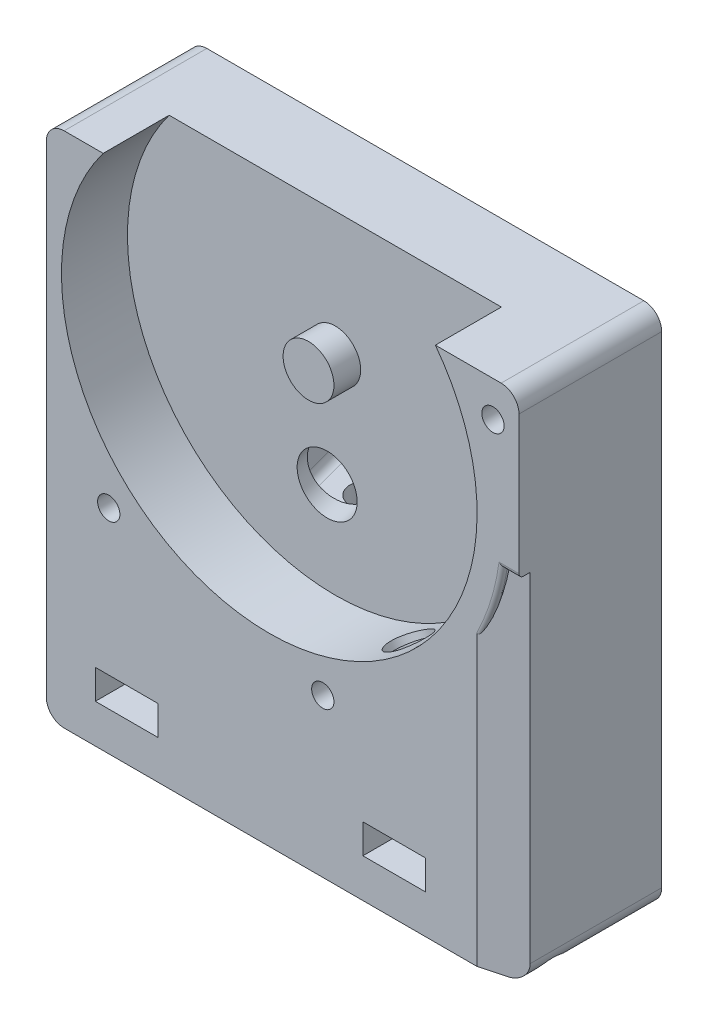
SolidWorks part; units mm, degrees
ref_plane "Front" through (0, 0, 0) normal (0, 0, 1) x (1, 0, 0)
ref_plane "Top" through (0, 0, 0) normal (0, 1, 0) x (1, 0, 0)
ref_plane "Right" through (0, 0, 0) normal (1, 0, 0) x (0, 0, -1)
sketch "Sketch1" plane through (0, 0, 0) normal (0, 0, 1) x (1, 0, 0)
  line L1 (-25, 27) -> (28, 27)
  line L2 (-25, 27) -> (-25, -31)
  line L3 (-25, -31) -> (28, -31)
  line L4 (28, 27) -> (28, -31)
  dimension "D1" = 58
  dimension "D2" = 53
  dimension "D3" = 31
  dimension "D4" = 25
extrude "Boss-Extrude1" add sketch "Sketch1" along normal blind 4 and the other way blind 12
sketch "Sketch2" plane through (0, 0, 0) normal (0, 0, 1) x (1, 0, 0)
  circle A1 centre (0, 13) radius 23.3
  dimension "D1" = 46.6
  dimension "D2" = 13
extrude "Cut-Extrude1" cut sketch "Sketch2" along normal blind 4 and the other way blind 3.4
sketch "Sketch3" plane through (0, 0, -3.4) normal (0, 0, 1) x (1, 0, 0)
  circle A0 centre (0, 13) radius 2.85
  arc A1 (-18.625, 27) -> (18.625, 27) centre (0, 13) ccw construction
  dimension "D1" = 5.7
extrude "Boss-Extrude2" add sketch "Sketch3" along normal blind 3
ref_plane "Plane1" through (0, 13, 0) normal (0, 1, 0) x (1, 0, 0)
ref_axis "Axis1" through (0, 13, -80.9) along (0, 0, 1)
ref_plane "Plane2" through (5.6292, 3.25, 0) normal (0.866, 0.5, 0) x (0, 0, 1)
ref_plane "Plane3" through (-5.6292, 9.75, 0) normal (-0.5, 0.866, 0) x (0, 0, 1)
ref_plane "Plane4" through (21.3708, -37.0154, 0) normal (-0.5, 0.866, 0) x (0, 0, 1)
sketch "Sketch4" plane through (21.3708, -37.0154, 0) normal (-0.5, 0.866, 0) x (0, 0, 1)
  line L0 (88.99, 6.5) -> (-88.99, 6.5) construction
  line L1 (4, 8.7487) -> (4, 37.7487) construction
  circle A0 centre (0, 6.5) radius 2.25
  dimension "D1" = 4.5
  dimension "D2" = 4
extrude "Cut-Extrude2" cut sketch "Sketch4" along normal blind 32
sketch "Sketch5" plane through (21.3708, -37.0154, 0) normal (-0.5, 0.866, 0) x (0, 0, 1)
  circle A0 centre (0, 6.5) radius 2.6
  arc A1 (-0.0761, 8.7487) -> (0.0761, 8.7487) centre (0, 6.5) ccw construction
  dimension "D1" = 5.2
extrude "Cut-Extrude3" cut sketch "Sketch5" along normal blind 30
ref_axis "Axis2" through (0, 50, 0) along (0, -1, 0)
ref_plane "Plane5" through (0, 0, 0) normal (0.2588, 0, 0.9659) x (0, -1, 0)
sketch "Sketch6" plane through (0, 0, 0) normal (0.2588, 0, 0.9659) x (0, -1, 0)
  circle A0 centre (0, 0) radius 3.25
  dimension "D1" = 6.5
extrude "Cut-Extrude4" cut sketch "Sketch6" against normal through all
ref_axis "Axis3" through (-3.3331, 0, -12.4392) along (0.2588, 0, 0.9659)
ref_plane "Plane6" through (-3.6235, 0, -13.523) normal (0.2588, 0, 0.9659) x (0, -1, 0)
sketch "Sketch10" plane through (-3.6235, 0, -13.523) normal (0.2588, 0, 0.9659) x (0, -1, 0)
  line L1 (4, 5) -> (-4, 5)
  line L2 (5, 4) -> (5, -4)
  line L3 (4, -5) -> (-4, -5)
  line L4 (-5, 4) -> (-5, -4)
  line L5 (5, 5) -> (-5, -5) construction
  line L6 (5, -5) -> (-5, 5) construction
  arc A0 (-4, 5) -> (-5, 4) centre (-4, 4) ccw
  arc A1 (-5, -4) -> (-4, -5) centre (-4, -4) ccw
  arc A2 (4, -5) -> (5, -4) centre (4, -4) ccw
  arc A3 (5, 4) -> (4, 5) centre (4, 4) ccw
  point P0 (0, 0)
  dimension "D3" = 1
  dimension "D1" = 10
  dimension "D2" = 10
extrude "Cut-Extrude5" cut sketch "Sketch10" along normal blind 8
sketch "Sketch11" plane through (0, -31, 0) normal (0, -1, 0) x (1, 0, 0)
  line L0 (-3.3331, -12.4392) -> (-0.1584, -0.591) construction
  line L1 (-5.4166, -4.7603) -> (2.3108, -6.8308) construction
  circle A0 centre (-2.5882, -9.6593) radius 1.5
  dimension "D1" = 3
  dimension "D2" = 4
extrude "Cut-Extrude6" cut sketch "Sketch11" against normal blind 27
sketch "Sketch12" plane through (0, -31, 0) normal (0, -1, 0) x (1, 0, 0)
  circle A0 centre (-2.5882, -9.6593) radius 2
  dimension "D1" = 4
extrude "Cut-Extrude7" cut sketch "Sketch12" against normal blind 27
sketch "Sketch13" plane through (0, 0, 4) normal (0, 0, 1) x (1, 0, 0)
  line L1 (0, -50) -> (0, 50) construction
  circle A0 centre (0, 13) radius 27 construction
  circle A1 centre (25.0799, 23) radius 1.25
  circle A2 centre (-18, -7.1246) radius 1.25
  circle A3 centre (6, -13.3249) radius 1.25
  dimension "D1" = 54
  dimension "D2" = 2.5
  dimension "D4" = 6
  dimension "D3" = 10
  dimension "D5" = 18
extrude "Cut-Extrude8" cut sketch "Sketch13" against normal blind 10
fillet "Fillet1" radius 2 4 edges at (-25, -31, -4) (-25, 27, -4) (28, 27, -4)
sketch "Sketch14" plane through (0, -31, 0) normal (0, -1, 0) x (1, 0, 0)
  line L0 (23.3, 4) -> (28, 2.7406)
  line L3 (28, 2.7406) -> (28, 4)
  line L4 (28, 4) -> (23.3, 4)
  line L5 (53.1259, -14.235) -> (-53.1259, 14.235) construction
extrude "Cut-Extrude9" cut sketch "Sketch14" against normal blind 40
sketch "Sketch15" plane through (0, 0, 4) normal (0, 0, 1) x (1, 0, 0)
  line L0 (23.2465, 11.422) -> (26.453, 11.422)
  line L1 (20.5971, 2.1073) -> (23.2465, 0.278)
  arc A0 (23.2465, 0.278) -> (26.453, 11.422) centre (0, 13) ccw
  arc A1 (20.5971, 2.1073) -> (23.2465, 11.422) centre (0, 13) ccw
  arc A2 (-18.625, 27) -> (18.625, 27) centre (0, 13) ccw construction
  dimension "D1" = 53
extrude "Boss-Extrude3" add sketch "Sketch15" against normal blind 3
fillet "Fillet3" radius 0.5 2 edges at (25.121, 4.5629, 4) (27.0982, 9, 4)
ref_plane "Plane7" through (0, -25, 0) normal (0, 1, 0) x (1, 0, 0)
sketch "Sketch17" plane through (0, -25, 0) normal (0, 1, 0) x (1, 0, 0)
  line L1 (-12.5, 6.0207) -> (-16, 8.0415)
  line L2 (-16, 8.0415) -> (-19.5, 6.0207)
  line L3 (-19.5, 6.0207) -> (-19.5, 1.9793)
  line L6 (-12.5, 1.9793) -> (-12.5, 6.0207)
  line L7 (17.5, 6.0207) -> (14, 8.0415)
  line L8 (14, 8.0415) -> (10.5, 6.0207)
  line L9 (10.5, 6.0207) -> (10.5, 1.9793)
  line L12 (17.5, 1.9793) -> (17.5, 6.0207)
  line L13 (-19.5, 1.9793) -> (-19.5, -4)
  line L14 (-23, -4) -> (23.3, -4) construction
  line L15 (-19.5, -4) -> (-12.5, -4)
  line L16 (-12.5, -4) -> (-12.5, 1.9793)
  line L17 (10.5, 1.9793) -> (10.5, -4)
  line L18 (10.5, -4) -> (17.5, -4)
  line L19 (17.5, -4) -> (17.5, 1.9793)
  line L20 (-19.4821, 1.9689) -> (-17.7321, 0.9585) [skipped]
  line L21 (-12.5179, 1.9689) -> (-10.7679, 2.9793) [skipped]
  line L22 (10.5179, 1.9689) -> (12.2679, 0.9585) [skipped]
  line L23 (17.4821, 1.9689) -> (19.2321, 2.9793) [skipped]
  circle A0 centre (-16, 4) radius 3.5 construction
  circle A1 centre (14, 4) radius 3.5 construction
  dimension "D1" = 7
  dimension "D2" = 8
  dimension "D3" = 16
  dimension "D4" = 14
extrude "Cut-Extrude11" cut sketch "Sketch17" against normal mid plane 3.3
sketch "Sketch18" plane through (0, -31, 0) normal (0, -1, 0) x (1, 0, 0)
  line L1 (-23, 4) -> (23.3, 4) construction
  circle A0 centre (-16, -4) radius 2.1
  circle A1 centre (14, -4) radius 2.1
  dimension "D1" = 4.2
  dimension "D2" = 8
  dimension "D3" = 16
  dimension "D4" = 14
extrude "Cut-Extrude12" cut sketch "Sketch18" against normal up to next
